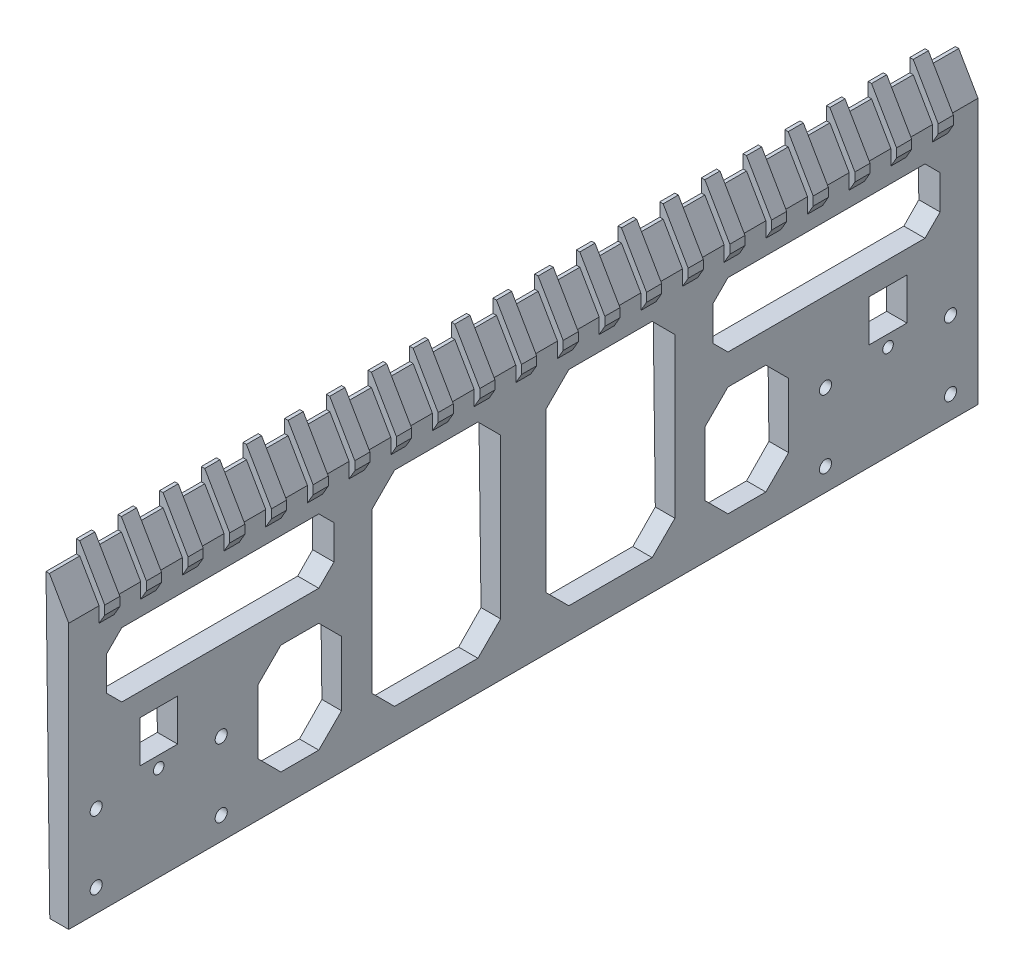
SolidWorks part; units mm, degrees
ref_plane "前视基准面" through (0, 0, 0) normal (0, 0, 1) x (1, 0, 0)
ref_plane "上视基准面" through (0, 0, 0) normal (0, 1, 0) x (1, 0, 0)
ref_plane "右视基准面" through (0, 0, 0) normal (1, 0, 0) x (0, 0, -1)
sketch "草图1" plane through (0, 0, 0) normal (1, 0, 0) x (0, 0, -1)
  line L1 (0, 0) -> (240, 0)
  line L2 (0, 0) -> (0, -70)
  line L3 (0, -70) -> (240, -70)
  line L4 (240, 0) -> (240, -70)
  dimension "D1" = 240
  dimension "D2" = 70
extrude "凸台-拉伸1" add sketch "草图1" along normal blind 6
sketch "草图3" plane through (6, 0, 0) normal (1, 0, 0) x (0, 0, -1)
  line L0 (120, 0) -> (120, -70) construction
  line L1 (14, -8) -> (66, -8)
  line L2 (10, -12) -> (10, -21)
  line L3 (14, -25) -> (66, -25)
  line L4 (70, -12) -> (70, -21)
  line L5 (240, 0) -> (0, 0) construction
  line L6 (0, -70) -> (240, -70) construction
  line L7 (0, 0) -> (0, -70) construction
  line L12 (10, -12) -> (14, -8)
  line L13 (10, -21) -> (14, -25)
  line L14 (66, -25) -> (70, -21)
  line L15 (66, -8) -> (70, -12)
  line L28 (80, -14) -> (86, -8)
  line L36 (50, -56) -> (56, -62)
  line L42 (86, -8) -> (108, -8)
  line L43 (80, -14) -> (80, -56)
  line L44 (86, -62) -> (108, -62)
  line L45 (114, -14) -> (114, -56)
  line L46 (108, -8) -> (114, -14)
  line L47 (108, -62) -> (114, -56)
  line L48 (80, -56) -> (86, -62)
  line L49 (56, -33) -> (66, -33)
  line L50 (50, -39) -> (50, -56)
  line L51 (56, -62) -> (66, -62)
  line L52 (72, -39) -> (72, -56)
  line L53 (66, -62) -> (72, -56)
  line L54 (66, -33) -> (72, -39)
  line L55 (50, -39) -> (56, -33)
  point P0 (10, -8)
  point P1 (70, -25)
  point P2 (10, -25)
  point P3 (70, -8)
  point P20 (80, -8)
  point P21 (114, -62)
  point P22 (80, -62)
  point P23 (114, -8)
  point P24 (50, -33)
  point P33 (72, -62)
  point P34 (50, -62)
  point P35 (72, -33)
  dimension "D1" = 10
  dimension "D2" = 8
  dimension "D3" = 17
  dimension "D4" = 60
  dimension "D5" = 8
  dimension "D6" = 8
  dimension "D7" = 54
  dimension "D12" = 80
  dimension "D13" = 6
  dimension "D14" = 34
  dimension "D15" = 10
  dimension "D16" = 8
  dimension "D21" = 8
  dimension "D22" = 29
  dimension "D23" = 22
extrude "切除-拉伸2" cut sketch "草图3" against normal through all
sketch "草图2" plane through (0, 0, 0) normal (1, 0, 0) x (0, 0, -1)
  line L1 (7.25, -46) -> (40.25, -46) construction
  line L2 (7.25, -46) -> (7.25, -64) construction
  line L3 (7.25, -64) -> (40.25, -64) construction
  line L4 (40.25, -46) -> (40.25, -64) construction
  line L5 (240, 0) -> (0, 0) construction
  line L6 (120, 0) -> (120, -70) construction
  line L7 (23.75, -27.5561) -> (23.75, -70.3632) construction
  line L8 (23.75, -27.5561) -> (23.75, -70.3632) construction
  circle A0 centre (7.25, -46) radius 1.55
  circle A1 centre (40.25, -64) radius 1.55
  circle A2 centre (40.25, -46) radius 1.55
  circle A3 centre (7.25, -64) radius 1.55
  point P8 (23.75, -46)
  dimension "D5" = 3.1
  dimension "D2" = 46
  dimension "D3" = 33
  dimension "D4" = 18
sketch "草图6" plane through (0, 0, 0) normal (0, 0, 1) x (1, 0, 0)
  line L0 (6, 0) -> (0, 0)
  line L1 (0, 0) -> (0, 8.8335)
  line L2 (0.9, 8.8335) -> (6, 0)
  line L3 (0, 8.8335) -> (0.9, 8.8335)
  line L4 (0, 8.8335) -> (0, 10.3923) construction
  line L5 (0, 10.3923) -> (0.9, 8.8335) construction
  dimension "D1" = 30
  dimension "D2" = 0.9
extrude "凸台-拉伸2" add sketch "草图6" against normal blind 240
ref_plane "基准面1" through (0, 0, -120) normal (0, 0, 1) x (1, 0, 0)
sketch "草图8" plane through (0, 0, -120) normal (0, 0, 1) x (1, 0, 0)
  line L0 (0, 10.3923) -> (0, 12.3335)
  line L1 (0.9, 12.3335) -> (7.5, 0.9019)
  line L2 (7.5, 0.9019) -> (7.5, -1.4019)
  line L3 (7.5, -4) -> (6, -4) construction
  line L4 (6, 0) -> (6, -70) construction
  line L5 (6, -4) -> (6, 0)
  line L6 (6, 0) -> (0.9, 8.8335) construction
  line L7 (6, 0) -> (0.9, 8.8335)
  line L8 (0, 12.3335) -> (0.9, 12.3335)
  line L9 (0, 12.3335) -> (0, 13.8923) construction
  line L10 (0, 13.8923) -> (0.9, 12.3335) construction
  line L11 (0, 10.3923) -> (0, 8.8335)
  line L12 (0, 8.8335) -> (0.9, 8.8335)
  line L13 (0.9, 8.8335) -> (0, 10.3923) construction
  line L14 (6, -4) -> (7.5, -1.4019)
  line L15 (7.5, -1.4019) -> (7.5, -4) construction
  dimension "D1" = 3.5
  dimension "D2" = 1.5
  dimension "D3" = 4
  dimension "D4" = 0.9
  dimension "D5" = 30
extrude "凸台-拉伸3" add sketch "草图8" along normal mid plane 4
pattern_linear "阵列(线性)1" count 11 spacing 11 along (0, 0, 1) count 11 spacing 11 along (0, 0, -1) of "凸台-拉伸3"
hole_wizard "打孔尺寸(%根据)内六角圆柱头螺钉的类型1" positions "草图14" profile "草图15" counterbore size "M3" standard "GB" end condition through all
sketch "草图14" plane through (0, 0, 0) normal (-1, 0, 0) x (0, 0, 1)
  point P0 (-40.25, -46)
  point P3 (-7.25, -46)
  point P6 (-7.25, -64)
  point P9 (-40.25, -64)
sketch "草图15" plane through (0, -46, -40.25) normal (0, 1, 0) x (0, 0, 1)
  line L0 (0, 0) -> (0, 7.5)
  line L1 (0, 7.5) -> (1.6, 7.5)
  line L3 (1.6, 7.5) -> (1.6, 3.4)
  line L4 (1.6, 3.4) -> (3, 3.4)
  line L5 (3, 3.4) -> (3, 0)
  line L7 (3, 0) -> (0, 0)
  line L11 (0, -6.35) -> (0, 107.95) construction
  dimension "通孔孔直径" = 3.2
  dimension "通孔孔深度" = 7.5
  dimension "柱形沉头孔直径" = 6
  dimension "柱形沉头孔深度" = 3.4
sketch "草图16" plane through (0, 0, 0) normal (-1, 0, 0) x (0, 0, 1)
  line L0 (-7.25, -46) -> (-40.25, -46) construction
  line L2 (0, -70) -> (-240, -70) construction
  line L3 (-23.75, -27.5561) -> (-23.75, -70.3632) construction
  circle A0 centre (-23.75, -45) radius 1.4
  point P6 (0, 0)
  point P7 (-23.75, -45)
  dimension "D1" = 2.8
  dimension "D2" = 25
extrude "切除-拉伸3" cut sketch "草图16" against normal blind 10
mirror "镜向1" about plane through (0, 0, -120) normal (0, 0, 1) of "打孔尺寸(%根据)内六角圆柱头螺钉的类型1"
mirror "镜向2" about plane through (0, 0, -120) normal (0, 0, 1) of "切除-拉伸3", "切除-拉伸2"
sketch "草图17" plane through (0, 0, 0) normal (-1, 0, 0) x (0, 0, 1)
  line L1 (-28.75, -31) -> (-18.75, -31)
  line L2 (-28.75, -31) -> (-28.75, -42)
  line L3 (-28.75, -42) -> (-18.75, -42)
  line L4 (-18.75, -31) -> (-18.75, -42)
  line L5 (-23.75, -27.5561) -> (-23.75, -70.3632) construction
  line L6 (0, -70) -> (-240, -70) construction
  line L7 (-120, -70) -> (-120, -8.018) construction
  line L8 (-211.25, -31) -> (-221.25, -31)
  line L9 (-211.25, -31) -> (-211.25, -42)
  line L10 (-211.25, -42) -> (-221.25, -42)
  line L11 (-221.25, -31) -> (-221.25, -42)
  line L12 (-23.75, -27.5561) -> (-23.75, -70.3632) construction
  dimension "D1" = 10
  dimension "D2" = 11
  dimension "D4" = 28
extrude "切除-拉伸4" cut sketch "草图17" against normal through all
sketch "草图18" plane through (0, 0, 0) normal (0, 0, 1) x (1, 0, 0)
  line L0 (0, -70) -> (1, -70)
  line L1 (6, -70) -> (0, -70) construction
  line L4 (1, -70) -> (0, 8.8335)
  line L5 (0, 8.8335) -> (0, -70)
  dimension "D1" = 1
extrude "切除-拉伸5" cut sketch "草图18" against normal up to next
